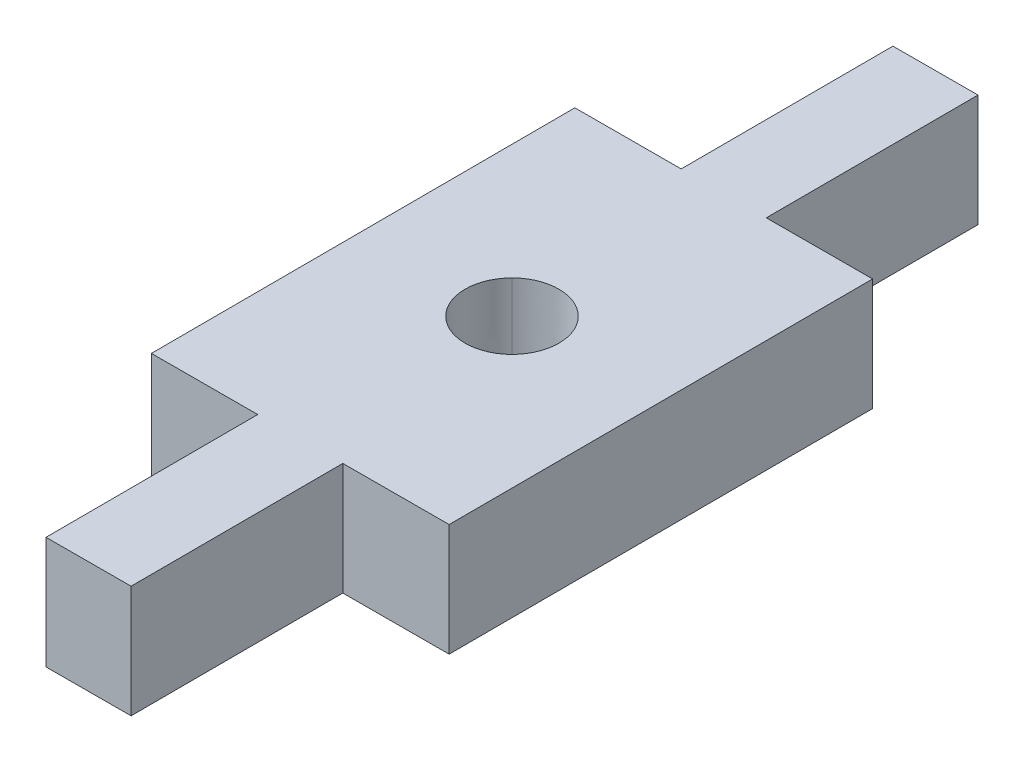
SolidWorks part; units mm, degrees
ref_plane "Front Plane" through (0, 0, 0) normal (0, 0, 1) x (1, 0, 0)
ref_plane "Top Plane" through (0, 0, 0) normal (0, 1, 0) x (1, 0, 0)
ref_plane "Right Plane" through (0, 0, 0) normal (1, 0, 0) x (0, 0, -1)
sketch "Sketch1" plane through (0, 0, 0) normal (0, 1, 0) x (1, 0, 0)
  line L75 (95.4278, 114.6068) -> (95.4412, 108.6068)
  line L76 (95.4412, 108.6068) -> (97.8412, 108.6122)
  line L77 (97.8412, 108.6122) -> (97.8276, 114.6122)
  line L78 (97.8276, 114.6122) -> (100.8277, 114.619)
  line L79 (100.8277, 114.619) -> (100.8008, 126.6189)
  line L80 (100.8008, 126.6189) -> (97.8008, 126.6122)
  line L81 (97.8008, 126.6122) -> (97.7874, 132.6122)
  line L82 (97.7874, 132.6122) -> (95.3874, 132.6068)
  line L83 (95.3874, 132.6068) -> (95.4009, 126.6068)
  line L84 (95.4009, 126.6068) -> (92.4008, 126.6)
  line L85 (92.4008, 126.6) -> (92.4278, 114.6002)
  line L86 (92.4278, 114.6002) -> (95.4278, 114.6068)
  spline S149 degree 3 poles (97.5489, 121.5485) (97.0305, 122.0647) (96.1915, 122.0629) (95.6752, 121.5443) knots 0 0 0 0 0.2 0.2 0.2 0.2
  spline S150 degree 3 poles (95.6752, 121.5443) (95.1589, 121.0258) (95.1609, 120.1867) (95.6795, 119.6705) knots 0.2 0.2 0.2 0.2 0.4 0.4 0.4 0.4
  spline S151 degree 3 poles (95.6795, 119.6705) (96.198, 119.1542) (97.037, 119.1562) (97.5532, 119.6748) knots 0.4 0.4 0.4 0.4 0.6 0.6 0.6 0.6
  spline S152 degree 3 poles (97.5532, 119.6748) (98.0696, 120.1933) (98.0676, 121.0322) (97.5489, 121.5485) knots 0.6 0.6 0.6 0.6 1 1 1 1
extrude "Boss-Extrude1" add sketch "Sketch1" along normal blind 3.175
